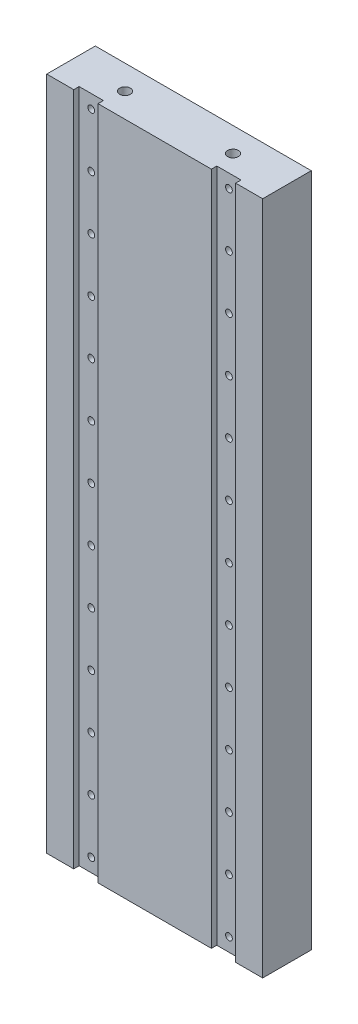
SolidWorks part; units mm, degrees
ref_plane "Alzado" through (0, 0, 0) normal (0, 0, 1) x (1, 0, 0)
ref_plane "Planta" through (0, 0, 0) normal (0, 1, 0) x (1, 0, 0)
ref_plane "Vista lateral" through (0, 0, 0) normal (1, 0, 0) x (0, 0, -1)
sketch "Croquis1" plane through (0, 0, 0) normal (0, 0, 1) x (1, 0, 0)
  line L1 (0, 0) -> (80, 0)
  line L2 (0, 0) -> (0, 250)
  line L3 (0, 250) -> (80, 250)
  line L4 (80, 0) -> (80, 250)
  dimension "D1" = 250
  dimension "D2" = 80
extrude "Saliente-Extruir1" add sketch "Croquis1" along normal blind 18
sketch "Croquis2" plane through (0, 0, 18) normal (0, 0, 1) x (1, 0, 0)
  line L0 (80, 250) -> (0, 250) construction
  line L1 (10, 0) -> (19, 0)
  line L2 (10, 0) -> (10, 250)
  line L3 (10, 250) -> (19, 250)
  line L4 (19, 0) -> (19, 250)
  line L5 (80, 0) -> (80, 250) construction
  line L6 (70, 0) -> (61, 0)
  line L7 (70, 0) -> (70, 250)
  line L8 (70, 250) -> (61, 250)
  line L9 (61, 0) -> (61, 250)
  line L10 (0, 250) -> (0, 0) construction
  dimension "D1" = 9
  dimension "D2" = 9
  dimension "D3" = 10
  dimension "D4" = 10
extrude "Cortar-Extruir1" cut sketch "Croquis2" against normal blind 2
hole_wizard "Taladro roscado M31" positions "Croquis3" profile "Croquis4" tap size "M3" standard "DIN"
sketch "Croquis3" plane through (0, 0, 16) normal (0, 0, 1) x (1, 0, 0)
  line L0 (19, 250) -> (10, 250) construction
  line L1 (0, 250) -> (0, 0) construction
  point P0 (14.5, 245)
  dimension "D1" = 5
  dimension "D2" = 14.5
sketch "Croquis4" plane through (14.5, 245, 16) normal (1, 0, 0) x (0, -1, 0)
  line L0 (0, 0) -> (0, 10.7511)
  line L1 (0, 10.7511) -> (1.25, 10)
  line L2 (1.25, 10) -> (1.25, 0)
  line L5 (1.25, 0) -> (0, 0)
  line L10 (0, 10.7511) -> (-1.25, 10) construction
  line L11 (0, -6.35) -> (0, 107.95) construction
  dimension "Diámetro de perforador para roscar" = 2.5
  dimension "Profundidad de perforador para roscar" = 10
  dimension "Ángulo de perforador" = 118
cosmetic thread "Rosca de taladro2" parameters "D1"=6, "D2"=3
pattern_linear "MatrizL1" count 13 spacing 20 along (0, -1, 0) count 2 spacing 51 along (1, 0, 0) of "Taladro roscado M31"
hole_wizard "Taladros de espiga de Ø4.0mm1" positions "Croquis5" profile "Croquis7" hole size "Ø4.0" standard "DIN"
sketch "Croquis5" plane through (0, 250, 0) normal (0, 1, 0) x (1, 0, 0)
  line L0 (80, 0) -> (0, 0) construction
  line L1 (0, -18) -> (0, 0) construction
  line L2 (80, -18) -> (80, 0) construction
  point P0 (60, -9)
  point P2 (20, -9)
  point P7 (0, 0)
  dimension "D1" = 9
  dimension "D2" = 9
  dimension "D3" = 20
  dimension "D4" = 20
sketch "Croquis7" plane through (60, 250, 9) normal (1, 0, 0) x (0, 0, 1)
  line L0 (0, 0) -> (0, 13.2017)
  line L1 (0, 13.2017) -> (2, 12)
  line L2 (2, 12) -> (2, 0)
  line L5 (2, 0) -> (0, 0)
  line L10 (0, 13.2017) -> (-2, 12) construction
  line L11 (0, -6.35) -> (0, 107.95) construction
  dimension "Diámetro de taladro" = 4
  dimension "Profundidad de taladro" = 12
  dimension "Ángulo de perforador" = 118
